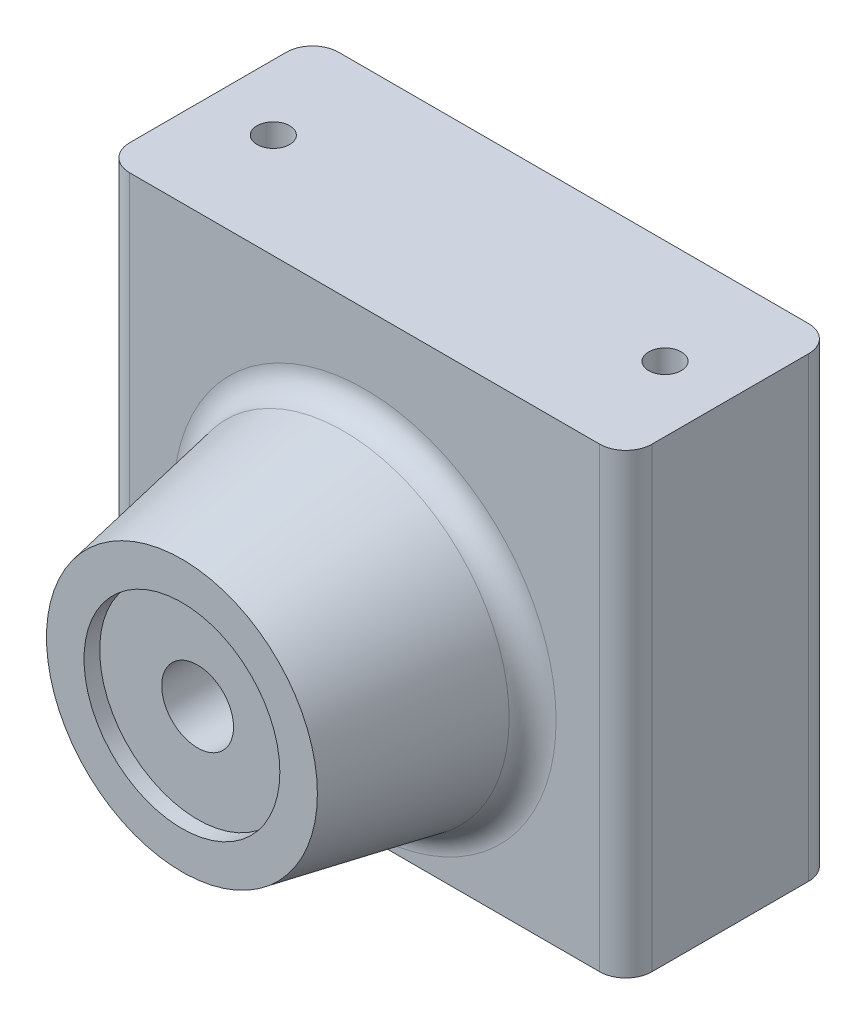
SolidWorks part; units mm, degrees
ref_plane "Спереди" through (0, 0, 0) normal (0, 0, 1) x (1, 0, 0)
ref_plane "Сверху" through (0, 0, 0) normal (0, 1, 0) x (1, 0, 0)
ref_plane "Справа" through (0, 0, 0) normal (1, 0, 0) x (0, 0, -1)
sketch "Эскиз1" plane through (0, 0, 0) normal (0, 0, 1) x (1, 0, 0)
  line L0 (0, 20) -> (0, -15) construction
  line L1 (-20, 20) -> (20, 20)
  line L2 (-20, 20) -> (-20, -15)
  line L3 (-20, -15) -> (20, -15)
  line L4 (20, 20) -> (20, -15)
  line L6 (-20, 0) -> (20, 0) construction
  dimension "D1" = 40
  dimension "D2" = 20
  dimension "D3" = 15
extrude "тело" add sketch "Эскиз1" against normal blind 16
sketch "Эскиз2" plane through (0, 0, 0) normal (0, 0, 1) x (1, 0, 0)
  circle A0 centre (0, 0) radius 10
  dimension "D1" = 20
extrude "утолщение оси" add sketch "Эскиз2" along normal blind 14
sketch "Эскиз4" plane through (0, 0, 14) normal (0, 0, 1) x (1, 0, 0)
  circle A0 centre (0, 0) radius 2.75
  dimension "D1" = 5.5
extrude "ось вращения" cut sketch "Эскиз4" against normal through all
chamfer "Фаска2" distance 3 distance2 16 1 edges at (10, 0, 0) first distance on face at (10, 0, 0)
fillet "Скругление5" radius 2 1 edges at (13, 0, 0)
sketch "Эскиз7" plane through (0, 20, 0) normal (0, 1, 0) x (1, 0, 0)
  line L0 (-20, 8) -> (20, 8) construction
  line L1 (-20, 16) -> (-20, 0) construction
  line L2 (20, 16) -> (20, 0) construction
  line L3 (0, 16) -> (0, 0) construction
  line L4 (20, 16) -> (-20, 16) construction
  circle A0 centre (-15, 8) radius 1.25
  circle A1 centre (15, 8) radius 1.25
  dimension "D1" = 2.5
  dimension "D2" = 30
extrude "отверстия для шурупов" cut sketch "Эскиз7" against normal through all
fillet "Скругление7" radius 2 4 edges at (20, 2.5, -16) (20, 2.5, 0) (-20, 2.5, -16) (-20, 2.5, 0)
sketch "Эскиз8" plane through (0, 0, 14) normal (0, 0, 1) x (1, 0, 0)
  circle A0 centre (0, 0) radius 7.5
  dimension "D1" = 15
extrude "углубление под шайбу" cut sketch "Эскиз8" against normal blind 1.2
sketch "Эскиз9" plane through (0, 0, -16) normal (0, 0, -1) x (-1, 0, 0)
  circle A0 centre (0, 0) radius 7.5
  dimension "D1" = 15
extrude "углубление под шайбу сзади" cut sketch "Эскиз9" against normal blind 1.5
